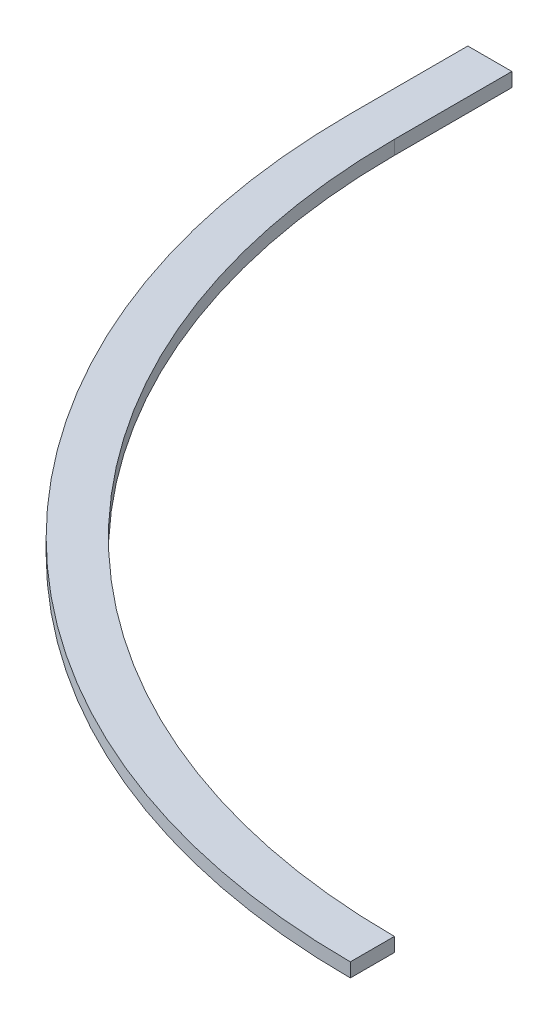
SolidWorks part; units mm, degrees
material "Pine"
ref_plane "Front Plane" through (0, 0, 0) normal (0, 0, 1) x (1, 0, 0)
ref_plane "Top Plane" through (0, 0, 0) normal (0, 1, 0) x (1, 0, 0)
ref_plane "Right Plane" through (0, 0, 0) normal (1, 0, 0) x (0, 0, -1)
sketch "Sketch2" plane through (0, 0, 0) normal (0, 1, 0) x (1, 0, 0)
  line L0 (0, 0) -> (-500, 0)
  line L1 (0, 0) -> (0, -500)
  circle A0 centre (0, 0) radius 500
  circle A1 centre (0, 0) radius 470
  dimension "D1" = 1000
  dimension "D2" = 30
extrude "Boss-Extrude1" add sketch "Sketch2" along normal blind 9.525 contours A1 L0 A0 L1 region at (-337.3402, 0, 337.3402)
sketch "Sketch3" plane through (0, 0, 0) normal (0, 0, -1) x (-1, 0, 0)
  line L8 (470, 0) -> (500, 0)
  line L9 (500, 0) -> (500, 9.525)
  line L10 (500, 9.525) -> (470, 9.525)
  line L11 (470, 9.525) -> (470, 0)
  line L12 (470, 0) -> (500, 0)
  line L13 (500, 0) -> (500, 9.525)
  line L14 (500, 9.525) -> (470, 9.525)
  line L15 (470, 9.525) -> (470, 0)
  dimension "D1" = 0
extrude "Boss-Extrude2" add sketch "Sketch3" along normal blind 80
